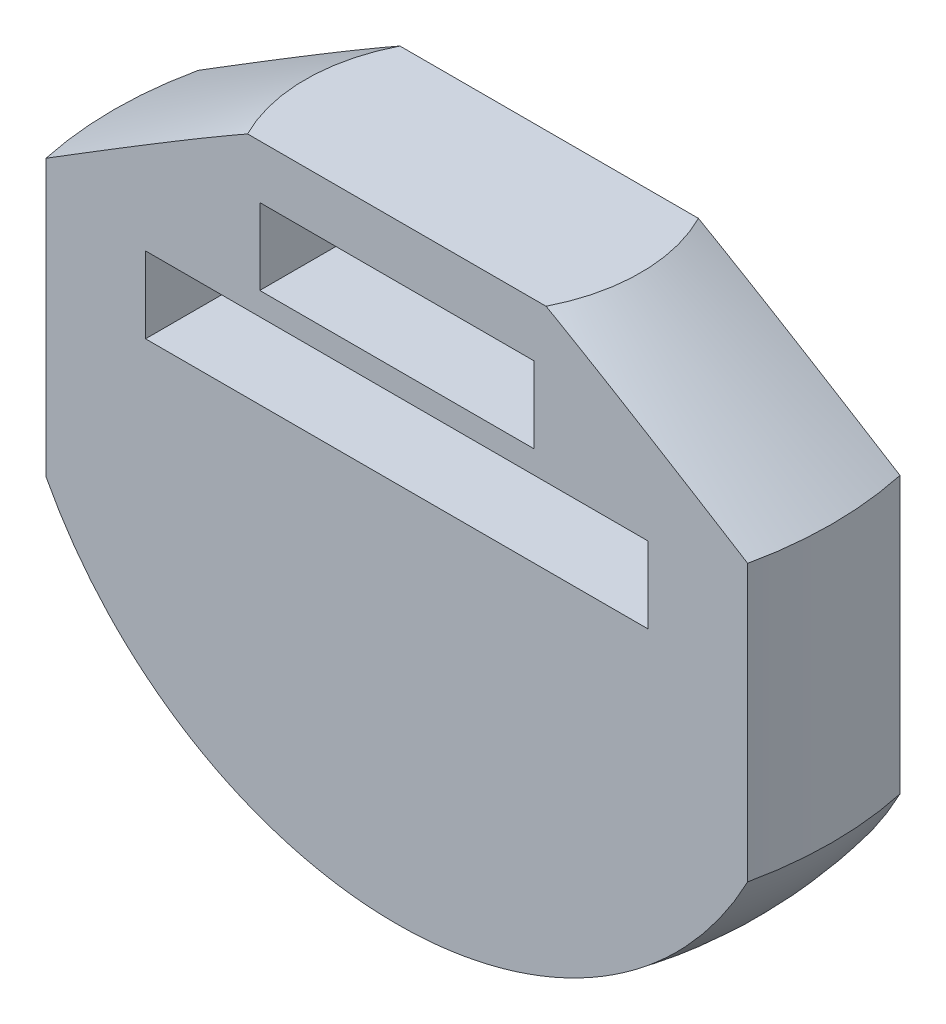
SolidWorks part; units mm, degrees
ref_plane "Front Plane" through (0, 0, 0) normal (0, 0, 1) x (1, 0, 0)
ref_plane "Top Plane" through (0, 0, 0) normal (0, 1, 0) x (1, 0, 0)
ref_plane "Right Plane" through (0, 0, 0) normal (1, 0, 0) x (0, 0, -1)
sketch "Sketch1" plane through (0, 0, 0) normal (0, 0, 1) x (1, 0, 0)
  line L0 (0, 0) -> (0, 18826.4255) construction
  line L1 (-23.57, -12.1122) -> (-23.57, 6)
  line L2 (0, 0) -> (50000, 0) construction
  line L5 (-11, 14) -> (0, 14)
  line L6 (0, 14) -> (0, -26.5)
  line L7 (0, 39.7364) -> (0, -39.7364)
  line L8 (-23.57, 6) -> (-11, 14)
  arc A0 (0, -26.5) -> (-23.57, -12.1122) centre (0, 0) cw
  arc A1 (0, 39.7364) -> (0, -39.7364) centre (0, 0) ccw
  arc A2 (-23.57, 12.1122) -> (0, 26.5) centre (0, 0) cw construction
  point P15 (-22.4718, 14)
  point P16 (0, 26.5)
  dimension "D1" = 26.5
  dimension "D4" = 26.5
  dimension "D2" = 23.57
  dimension "D3" = 6
  dimension "D5" = 14
extrude "Boss-Extrude2" add sketch "Sketch1" along normal mid plane 10 contours A0 L6 L5 L1 region at (-10.5601, -5.3927, 0)
mirror "Mirror2" about plane through (0, 0, 0) normal (1, 0, 0) of "Boss-Extrude2"
revolve "Cut-Revolve2" cut sketch "Sketch1<6>" angle 360 about L0 region at (-14.2701, -23.3772, 0)
sketch "Sketch1<6>" plane through (0, 0, 0) normal (0, 0, 1) x (1, 0, 0) same geometry as "Sketch1"
ref_plane "Plane1" through (0, 0, 0) normal (-0.7071, 0, 0.7071) x (0.7071, 0, 0.7071)
sketch "Sketch2" plane through (0, 0, 0) normal (0, 0, 1) x (1, 0, 0)
  line L0 (0, 0) -> (0, 50000) construction
  line L1 (0, 0) -> (50000, 0) construction
  line L2 (-11, 14) -> (-11, 6) construction
  line L3 (-9, 10.5) -> (9, 10.5)
  line L4 (-9, 10.5) -> (-9, 5.5)
  line L5 (-9, 5.5) -> (9, 5.5)
  line L6 (9, 10.5) -> (9, 5.5)
  line L8 (-23.0336, 6) -> (-23.0336, -12.1122)
  line L9 (23.0336, -12.1122) -> (23.0336, 6)
  line L10 (-16.5, -1) -> (16.5, -1)
  line L11 (-16.5, -1) -> (-16.5, 4)
  line L12 (9.798, 14) -> (-9.798, 14)
  line L13 (-16.5, 4) -> (16.5, 4)
  line L15 (-23.0336, 6) -> (-23.0336, -12.1122)
  line L16 (23.0336, -12.1122) -> (23.0336, 6)
  line L19 (9.798, 14) -> (-9.798, 14)
  line L21 (-9, 10.5) -> (9, 5.5) construction
  line L22 (-9, 5.5) -> (9, 10.5) construction
  line L23 (16.5, -1) -> (16.5, 4)
  line L24 (-16.5, -1) -> (16.5, 4) construction
  line L25 (-16.5, 4) -> (16.5, -1) construction
  arc A1 (-23.0336, -12.1122) -> (23.0336, -12.1122) centre (0, 0) ccw
  arc A3 (-23.0336, -12.1122) -> (23.0336, -12.1122) centre (0, 0) ccw
  spline S2 degree 3 poles (1972.5491, 2254.1641) (262.3638, -228.0412) (159.0609, -76.7816) (15.3496, 10.7286) (14.2463, 11.395) (-59.3517, 55.1725) (-150.4091, 67.9726) (-1411.6628, -2620.7307) knots -31.886157 -31.886157 -31.886157 -31.886157 0.5 0.5 0.75 0.75 17.108831 17.108831 17.108831 17.108831 only from (23.0336, 6) to (9.798, 14)
  spline S3 degree 3 poles (23.0336, 6) (20.8445, 7.3615) (18.6522, 8.7175) (15.3496, 10.7286) (14.2463, 11.395) (12.0307, 12.7129) (10.9186, 13.3647) (9.798, 14) knots 0 0 0 0 0.5 0.5 0.75 0.75 1 1 1 1
  spline S4 degree 3 poles (1520.9891, -2559.028) (148.8881, 66.9998) (59.4102, 55.2071) (-14.2459, 11.3953) (-15.3492, 10.7288) (-159.0507, -76.7753) (-262.2878, -227.9863) (-1974.5848, 2252.3516) knots -16.12082 -16.12082 -16.12082 -16.12082 0.25 0.25 0.5 0.5 32.882083 32.882083 32.882083 32.882083 only from (-9.798, 14) to (-23.0336, 6)
  spline S5 degree 3 poles (-9.798, 14) (-10.9183, 13.3649) (-12.0301, 12.7132) (-14.2459, 11.3953) (-15.3492, 10.7288) (-18.652, 8.7177) (-20.8444, 7.3615) (-23.0336, 6) knots 0 0 0 0 0.25 0.25 0.5 0.5 1 1 1 1
  point P0 (-9, 5.1662)
  point P2 (0, 0)
  point P4 (0, 8)
  point P23 (0, 1.5)
  dimension "D2" = 18
  dimension "D3" = 5
  dimension "D4" = 3.5
  dimension "D5" = 2
  dimension "D6" = 4
  dimension "D7" = 33
  dimension "D8" = 5
  dimension "D9" = 1.5
  dimension "D1" = 0
extrude "Cut-Extrude1" cut sketch "Sketch2" against normal through all both and the other way through all contours L3 L5 | L5 L6 L3 | L3 L4 L5 | L10 L23 L13 L11 region at (0, 8, 0) region at (0, 1.5, 0)
equation "\"D3@Sketch1\"=4+2mm"
